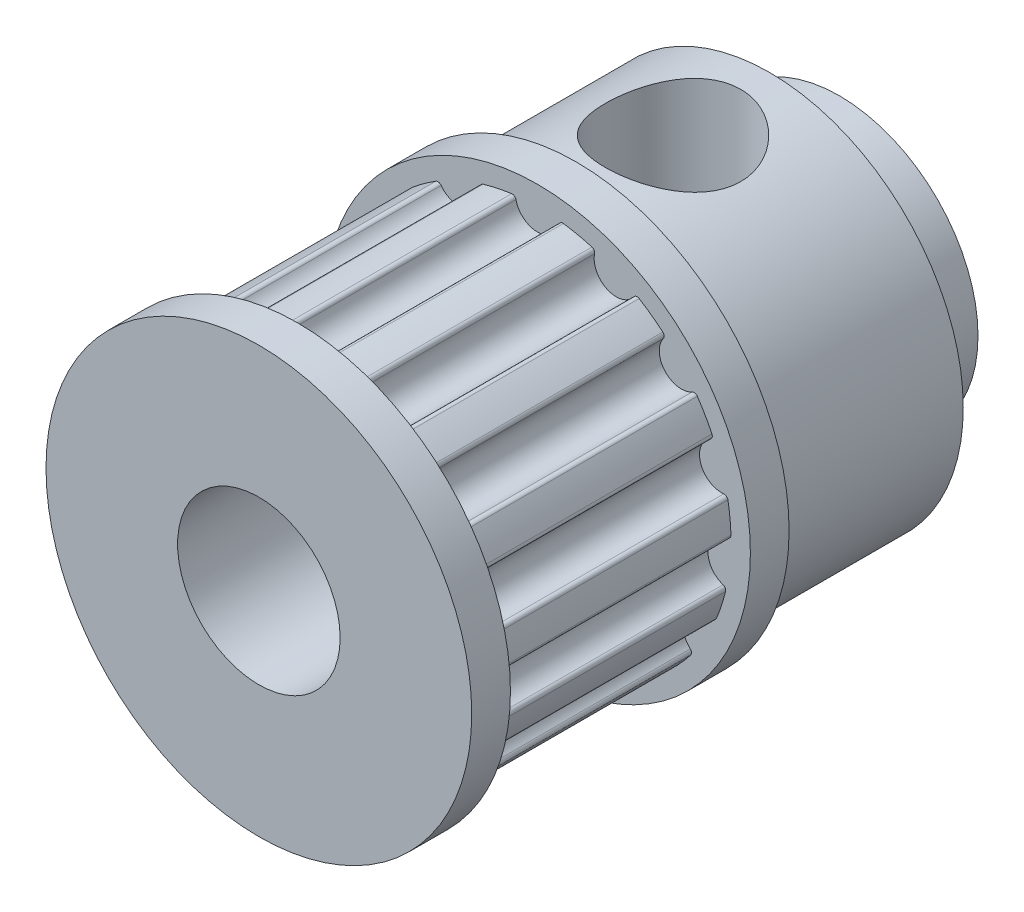
SolidWorks part; units mm, degrees
ref_plane "Plano frontal" through (0, 0, 0) normal (0, 0, 1) x (1, 0, 0)
ref_plane "Plano superior" through (0, 0, 0) normal (0, 1, 0) x (1, 0, 0)
ref_plane "Plano direito" through (0, 0, 0) normal (1, 0, 0) x (0, 0, -1)
sketch "Esboço1" plane through (0, 0, 0) normal (0, 0, 1) x (1, 0, 0)
  circle A0 centre (0, 0) radius 5
  circle A1 centre (0, 0) radius 2.1
  dimension "D1" = 4.2
  dimension "D2" = 10
extrude "Ressalto-extrusão1" add sketch "Esboço1" along normal blind 13.2
sketch "Esboço2" plane through (0, 0, 13.2) normal (0, 0, 1) x (1, 0, 0)
  circle A0 centre (0, 0) radius 2.1
  circle A1 centre (0, 0) radius 3.581
  circle A2 centre (0, 0) radius 2.1 construction
  dimension "D1" = 7.162
extrude "Ressalto-extrusão2" add sketch "Esboço2" against normal blind 15
ref_plane "Plano2" through (0, 0, 5) normal (0, 0, -1) x (-1, 0, 0)
sketch "Esboço7" plane through (0, 0, 13.2) normal (0, 0, 1) x (1, 0, 0)
  line L0 (0, 0) -> (0, 5) construction
  line L1 (0, 0) -> (2.0337, 4.5677) construction
  circle A0 centre (0, 5) radius 0.57
  circle A1 centre (0, 0) radius 5 construction
  circle A2 centre (2.0337, 4.5677) radius 0.57
  circle A3 centre (3.7157, 3.3457) radius 0.57
  circle A4 centre (4.7553, 1.5451) radius 0.57
  circle A5 centre (4.9726, -0.5226) radius 0.57
  circle A6 centre (4.3301, -2.5) radius 0.57
  circle A7 centre (2.9389, -4.0451) radius 0.57
  circle A8 centre (1.0396, -4.8907) radius 0.57
  circle A9 centre (-1.0396, -4.8907) radius 0.57
  circle A10 centre (-2.9389, -4.0451) radius 0.57
  circle A11 centre (-4.3301, -2.5) radius 0.57
  circle A12 centre (-4.9726, -0.5226) radius 0.57
  circle A13 centre (-4.7553, 1.5451) radius 0.57
  circle A14 centre (-3.7157, 3.3457) radius 0.57
  circle A15 centre (-2.0337, 4.5677) radius 0.57
  dimension "D3" = 1.14
  dimension "D2" = 24
  dimension "D1" = 15
extrude "Corte-extrusão2" cut sketch "Esboço7" against normal blind 8
fillet "Filete1" radius 0.1 30 edges at (-1.5006, 4.7695, 9.2) (-0.5691, 4.9675, 9.2) (-2.4594, -4.3533, 9.2) (-4.0175, -2.9766, 9.2) (-4.8808, -1.0852, 9.2) (-4.5865, -1.9909, 9.2) (-3.3802, -3.6843, 9.2) (0.4762, -4.9773, 9.2) (-1.5894, -4.7406, 9.2) (1.5894, -4.7406, 9.2) (2.4594, -4.3533, 9.2) (-0.4762, -4.9773, 9.2) (-4.9998, 0.0467, 9.2) (-4.9002, 0.9938, 9.2) (3.3802, -3.6843, 9.2) (4.0175, -2.9766, 9.2) (4.5865, -1.9909, 9.2) (4.8808, -1.0852, 9.2) (4.9998, 0.0467, 9.2) (4.9002, 0.9938, 9.2) (4.5485, 2.0763, 9.2) (4.0724, 2.901, 9.2) (3.3108, 3.7468, 9.2) (2.5403, 4.3066, 9.2) (-4.5485, 2.0763, 9.2) (-4.0724, 2.901, 9.2) (-3.3108, 3.7468, 9.2) (-2.5403, 4.3066, 9.2) (1.5006, 4.7695, 9.2) (0.5691, 4.9675, 9.2)
sketch "Esboço3" plane through (0, 0, 5) normal (0, 0, -1) x (-1, 0, 0)
  circle A1 centre (0, 0) radius 5.5
  circle A2 centre (0, 0) radius 2.1
  circle A3 centre (0, 0) radius 2.1 construction
  dimension "D1" = 11
extrude "Ressalto-extrusão3" add sketch "Esboço3" against normal blind 1
sketch "Esboço4" plane through (0, 0, 13.2) normal (0, 0, 1) x (1, 0, 0)
  circle A0 centre (0, 0) radius 2.1
  circle A1 centre (0, 0) radius 5.5
  circle A2 centre (0, 0) radius 5.5 construction
  circle A3 centre (0, 0) radius 2.1 construction
extrude "Ressalto-extrusão4" add sketch "Esboço4" against normal blind 1
ref_plane "Plano1" through (0, 0, 12.5) normal (0, 0, 1) x (1, 0, 0)
sketch "Esboço6" plane through (0, 0, 0) normal (0, 1, 0) x (1, 0, 0)
  line L0 (0, 0) -> (0, -5) construction
  line L1 (5.5, -5) -> (-5.5, -5) construction
  circle A0 centre (0, -2.5) radius 1.75
  dimension "D1" = 3.5
extrude "Corte-extrusão1" cut sketch "Esboço6" along normal through all
fillet "Filete2" radius 0.5 1 edges at (2.1, 0, -1.8)
